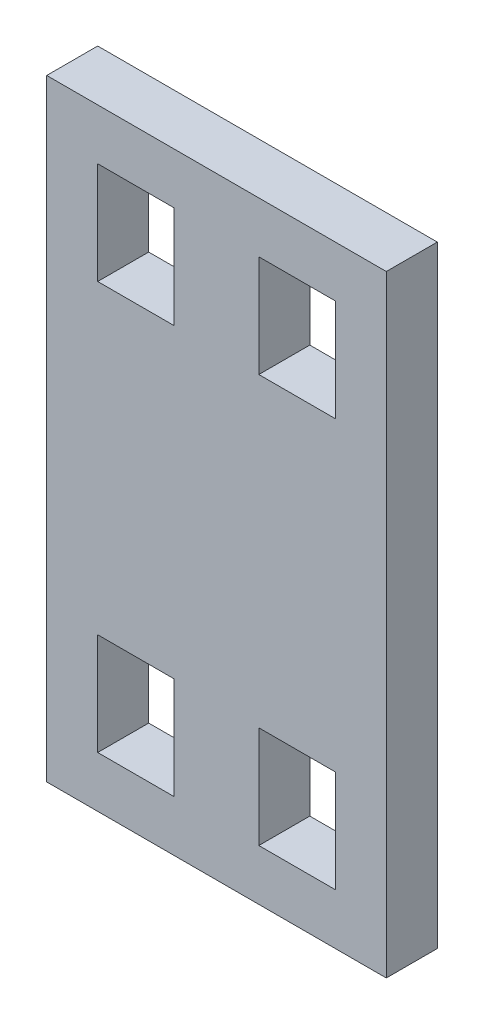
SolidWorks part; units mm, degrees
ref_plane "Front Plane" through (0, 0, 0) normal (1, 0, 0) x (0, 1, 0)
ref_plane "Top Plane" through (0, 0, 0) normal (0, 0, 1) x (0, 1, 0)
ref_plane "Right Plane" through (0, 0, 0) normal (0, 1, 0) x (-1, 0, 0)
sketch "Sketch1" plane through (0, 0, 0) normal (0, 0, 1) x (0, 1, 0)
  line L1 (0, 0) -> (76.2, 0)
  line L2 (0, 0) -> (0, 42.291)
  line L3 (0, 42.291) -> (76.2, 42.291)
  line L4 (76.2, 0) -> (76.2, 42.291)
  dimension "D1" = 76.2
  dimension "D2" = 42.291
extrude "Boss-Extrude1" add sketch "Sketch1" along normal blind 6.35
sketch "Sketch2" plane through (0, 0, 6.35) normal (0, 0, 1) x (1, 0, 0)
  line L0 (-21.1455, 0) -> (-21.1455, 76.2) construction
  line L1 (-42.291, 0) -> (0, 0) construction
  line L2 (0, 76.2) -> (-42.291, 76.2) construction
  line L3 (-21.1455, 38.1) -> (0, 38.1) construction
  line L4 (-26.416, 6.35) -> (-35.941, 6.35)
  line L5 (-26.416, 6.35) -> (-26.416, 19.05)
  line L6 (-26.416, 19.05) -> (-35.941, 19.05)
  line L7 (-35.941, 6.35) -> (-35.941, 19.05)
  line L8 (-26.416, 6.35) -> (-35.941, 19.05) construction
  line L9 (-26.416, 19.05) -> (-35.941, 6.35) construction
  line L10 (-6.35, 57.15) -> (-15.875, 57.15)
  line L11 (0, 0) -> (0, 76.2) construction
  line L12 (-26.416, 57.15) -> (-35.941, 57.15)
  line L13 (-35.941, 69.85) -> (-35.941, 57.15)
  line L14 (-26.416, 69.85) -> (-35.941, 69.85)
  line L15 (-26.416, 69.85) -> (-26.416, 57.15)
  line L16 (-21.1455, 38.1) -> (-42.291, 38.1) construction
  line L17 (-42.291, 76.2) -> (-42.291, 0) construction
  line L18 (-15.875, 69.85) -> (-15.875, 57.15)
  line L19 (-6.35, 6.35) -> (-15.875, 6.35)
  line L20 (-6.35, 6.35) -> (-6.35, 19.05)
  line L21 (-6.35, 19.05) -> (-15.875, 19.05)
  line L22 (-15.875, 6.35) -> (-15.875, 19.05)
  line L23 (-6.35, 6.35) -> (-15.875, 19.05) construction
  line L24 (-6.35, 19.05) -> (-15.875, 6.35) construction
  line L25 (-6.35, 69.85) -> (-15.875, 69.85)
  line L26 (-6.35, 69.85) -> (-6.35, 57.15)
  point P6 (-25.4, 12.7)
  point P23 (-11.1125, 12.7)
  dimension "D1" = 9.525
  dimension "D2" = 12.7
  dimension "D3" = 6.35
  dimension "D4" = 6.35
  dimension "D6" = 12.7
  dimension "D5" = 9.525
  dimension "D7" = 10.541
extrude "Cut-Extrude1" cut sketch "Sketch2" against normal through all
equation "\"shaft_len\"= 1in"
equation "\"ouput_shaft_d\"= 0.25"
equation "\"input_shaft_d\" = 0.125in"
equation "\"pinion_pitch\"= 3 / 8in"
equation "\"gear_pitch\"= 1in"
equation "\"pitch_tot\"= \"pinion_pitch\" + \"gear_pitch\""
equation "\"sleeve_len\"= 3 / 8in"
equation "\"pinion_sleeve_d\"= 1 / 4in"
equation "\"gear_sleeve_d\"= 3 / 8in"
equation "\"D1@Sketch2\"=\"sleeve_len\""
equation "\"slot_dist\"= 0.375 + 0.02*2"
equation "\"D7@Sketch2\"=\"slot_dist\""
equation "\"D2@Sketch1\"=\"slot_dist\"+\"sleeve_len\"*2+.25*2"
